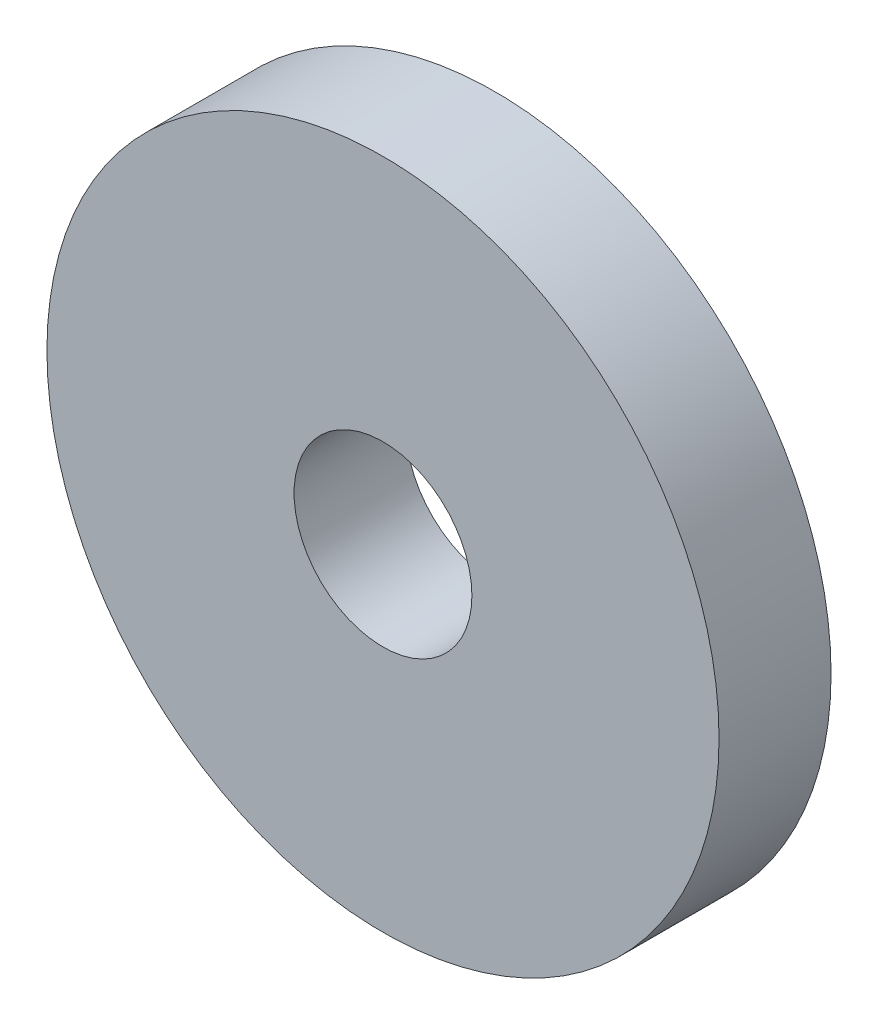
SolidWorks part; units mm, degrees
material "Delrin 2700 NC010, Low Viscosity Acetal Copolymer (SS)"
ref_plane "Front" through (0, 0, 0) normal (0, 0, 1) x (1, 0, 0)
ref_plane "Top" through (0, 0, 0) normal (0, 1, 0) x (1, 0, 0)
ref_plane "Right" through (0, 0, 0) normal (1, 0, 0) x (0, 0, -1)
ref_axis "side-side" through (80.9, 0, 0) along (-1, 0, 0)
ref_axis "up-down" through (0, 50, 0) along (0, -1, 0)
ref_axis "front-back" through (0, 0, -80.9) along (0, 0, 1)
sketch "Sketch1" plane through (0, 0, 0) normal (0, 0, 1) x (1, 0, 0)
  circle A0 centre (0, 0) radius 3.175
  circle A1 centre (0, 0) radius 12
  dimension "D1" = 6.35
  dimension "D2" = 24
extrude "Boss-Extrude1" add sketch "Sketch1" along normal blind 4
